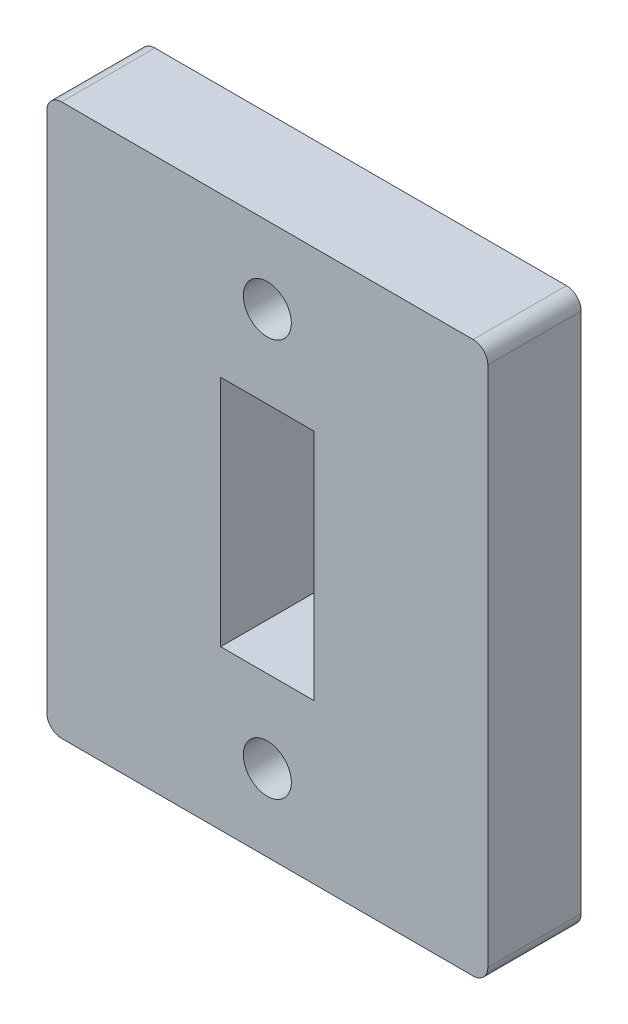
SolidWorks part; units mm, degrees
ref_plane "Front Plane" through (0, 0, 0) normal (0, 0, 1) x (1, 0, 0)
ref_plane "Top Plane" through (0, 0, 0) normal (0, 1, 0) x (1, 0, 0)
ref_plane "Right Plane" through (0, 0, 0) normal (1, 0, 0) x (0, 0, -1)
sketch "Sketch1" plane through (0, 0, 0) normal (0, 0, 1) x (1, 0, 0)
  line L0 (60, -37.5) -> (0, -37.5) construction
  line L1 (0, 0) -> (60, 0)
  line L2 (0, 0) -> (0, -75)
  line L3 (0, -75) -> (60, -75)
  line L4 (60, 0) -> (60, -75)
  line L5 (30, -37.5) -> (30, -21.625) construction
  line L6 (30, -21.625) -> (36.35, -21.625)
  line L7 (36.35, -21.625) -> (36.35, -53.375)
  line L8 (36.35, -53.375) -> (30, -53.375)
  line L9 (30, -53.375) -> (23.65, -53.375)
  line L10 (23.65, -53.375) -> (23.65, -21.625)
  line L11 (23.65, -21.625) -> (30, -21.625)
  line L12 (30, -37.5) -> (30, -53.375) construction
  line L13 (30, 0) -> (30, -13.25) construction
  line L14 (30, -75) -> (30, -64.56) construction
  dimension "D1" = 75
  dimension "D2" = 60
  dimension "D3" = 12.7
  dimension "D4" = 31.75
  dimension "D5" = 13.25
  dimension "D6" = 10.44
extrude "Boss-Extrude1" add sketch "Sketch1" along normal blind 12.7
sketch "Sketch4" plane through (0, 0, 0) normal (0, 0, -1) x (-1, 0, 0)
  line L0 (-30, 0) -> (-30, -10.44)
  line L1 (-60, 0) -> (0, 0) construction
  line L2 (-30, -75) -> (-30, -64.56)
  line L3 (0, -75) -> (-60, -75) construction
  dimension "D1" = 10.44
  dimension "D2" = 10.44
hole_wizard "CSK for 1/4 Flat Head Machine Screw1" positions "Sketch5" profile "Sketch6" countersink size "1/4" standard "ANSI Inch" end condition through all
sketch "Sketch5" plane through (0, 0, 0) normal (0, 0, -1) x (-1, 0, 0)
  point P0 (-30, -10.44)
  point P3 (-30, -64.56)
sketch "Sketch6" plane through (30, -10.44, 0) normal (1, 0, 0) x (0, 1, 0)
  line L0 (0, 0) -> (0, 12.7)
  line L1 (0, 12.7) -> (3.2639, 12.7)
  line L2 (3.2639, 12.7) -> (3.2639, 3.6524)
  line L3 (3.2639, 3.6524) -> (6.4389, 0)
  line L5 (6.4389, 0) -> (0, 0)
  line L6 (-3.2639, 3.6524) -> (-6.4389, 0) construction
  line L11 (0, -6.35) -> (0, 107.95) construction
  dimension "Thru Hole Dia." = 6.5278
  dimension "Thru Hole Depth" = 12.7
  dimension "Near C'Sink Dia." = 12.8778
  dimension "Near C'Sink Angle" = 82
fillet "Fillet1" radius 2 4 edges at (0, 0, 6.35) (60, 0, 6.35) (0, -75, 6.35) (60, -75, 6.35)
